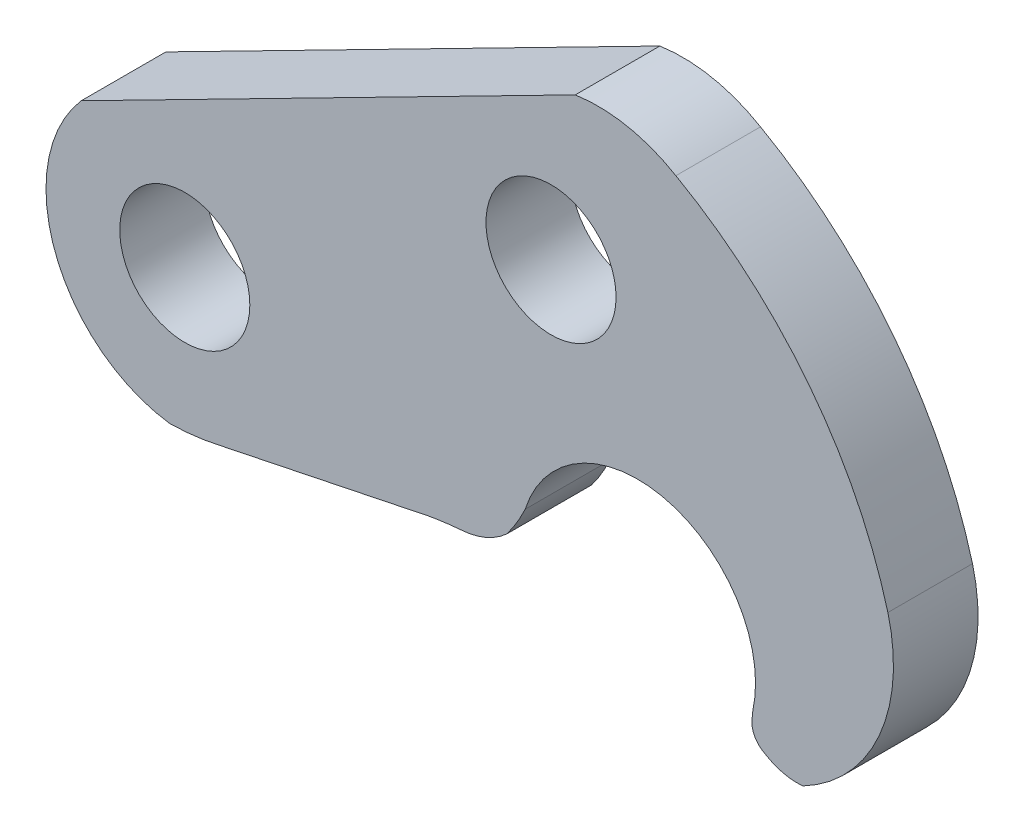
SolidWorks part; units mm, degrees
ref_plane "Ön Düzlem" through (0, 0, 0) normal (0, 0, 1) x (1, 0, 0)
ref_plane "Üst Düzlem" through (0, 0, 0) normal (0, 1, 0) x (1, 0, 0)
ref_plane "Sağ Düzlem" through (0, 0, 0) normal (1, 0, 0) x (0, 0, -1)
sketch "Çizim1" plane through (0, 0, 0) normal (0, 0, 1) x (1, 0, 0)
  line L0 (11.8452, 101.7754) -> (219.8965, 207.9447) construction
  line L1 (2.0475, 0.8271) -> (315.9238, -7.9864) construction
  line L2 (24.1343, 108.0088) -> (315.9238, -7.9864) construction
  line L3 (150.0986, 172.366) -> (315.9238, -7.9864) construction
  line L4 (222.8704, 138.8703) -> (194.2898, 194.8775) construction
  line L5 (-1.6434, 91.6588) -> (231.8747, 210.8239)
  line L6 (13.1543, 99.2101) -> (221.2056, 205.3794) construction
  line L7 (63.8942, -16.6878) -> (162.1718, 3.6692)
  line L8 (315.5, -2.5671) -> (315.805, 0.498)
  line L9 (47.2968, 47.8913) -> (222.8704, 138.8703) construction
  circle A1 centre (47.2968, 47.8913) radius 33 construction
  circle A2 centre (47.2968, 47.8913) radius 30.75
  circle A3 centre (222.8704, 138.8703) radius 32.5 construction
  circle A4 centre (222.8704, 138.8703) radius 30.75 construction
  arc A5 (219.8965, 207.9447) -> (279.4607, 201.5265) centre (242.6599, 139.5986) cw construction
  arc A6 (279.4607, 201.5265) -> (379.6777, 72.811) centre (175.7647, 17.4176) cw
  arc A7 (339.489, -18.3062) -> (379.6777, 72.811) centre (302.4564, 52.4491) ccw
  arc A8 (231.8747, 210.8239) -> (279.4607, 201.5265) centre (242.6599, 139.5986) cw
  arc A9 (0, 93.4718) -> (40.1287, -19.5749) centre (49.1466, 47.2719) ccw construction
  arc A10 (-1.6434, 91.6588) -> (40.1287, -19.5749) centre (49.1466, 47.2719) ccw
  arc A11 (40.1287, -19.5749) -> (63.8942, -16.6878) centre (38.3335, 94.458) ccw
  arc A12 (162.1718, 3.6692) -> (177.9597, 5.7281) centre (190.0135, -148.2593) cw
  arc A13 (177.9597, 5.7281) -> (199.5896, 14.9647) centre (175.7251, 40.9055) ccw
  circle A14 centre (261.3643, 10.7515) radius 56.8865 construction
  arc A17 (321.2542, -13.8642) -> (315.5, -2.5671) centre (326.2916, -4.1845) cw
  arc A18 (321.2542, -13.8642) -> (339.489, -18.3062) centre (336.8496, 10.5079) ccw
  arc A19 (199.5896, 14.9647) -> (208.2239, 29.3667) centre (134.7843, 63.6059) ccw
  arc A20 (315.805, 0.498) -> (208.2239, 29.3667) centre (261.3643, 12.5096) ccw
  circle A21 centre (220.4328, 137.6072) radius 30.75
  dimension "D1" = 66
  dimension "D5" = 61.5
  dimension "D6" = 65
  dimension "D10" = 113.773
  dimension "D11" = 55.75
  dimension "D13" = 61.5
  dimension "D2" = 314
  dimension "D3" = 314
  dimension "D4" = 245
  dimension "D7" = 197.7454
  dimension "D8" = 62.8781
  dimension "D12" = 59.9981
  dimension "D14" = 195
  dimension "D9" = 2.88
base flange "Taban-Flanş1" sketch "Çizim1" thickness 40 reverse thickness direction no parameters "D1"=6
sketch "Büküm-Çizgileri1" [suppressed] plane through (0, 0, 0) normal (0, 1, 0) x (1, 0, 0)
sketch "Sınırlandırma-Kutusu1" [suppressed] plane through (0, 0, 0) normal (0, 1, 0) x (1, 0, 0)
sheet metal parameters "Sac-Levha1" thickness 40 parameters "D1"=6
flat pattern "Düz-Çoğaltma1" [suppressed]
sketch "Büküm-Çizgileri2" plane through (0, 0, 0) normal (0, 1, 0) x (1, 0, 0)
sketch3d "Sınırlandırma-Kutusu2" [suppressed]
  line L0 (-260.7067, -159.3986, 0) -> (139.9313, -157.8487, 0) construction
  line L1 (-261.5981, 71.0257, 0) -> (139.0398, 72.5756, 0) construction
  line L2 (-260.7067, -159.3986, 0) -> (-261.5981, 71.0257, 0) construction
  line L3 (139.9313, -157.8487, 0) -> (139.0398, 72.5756, 0) construction
